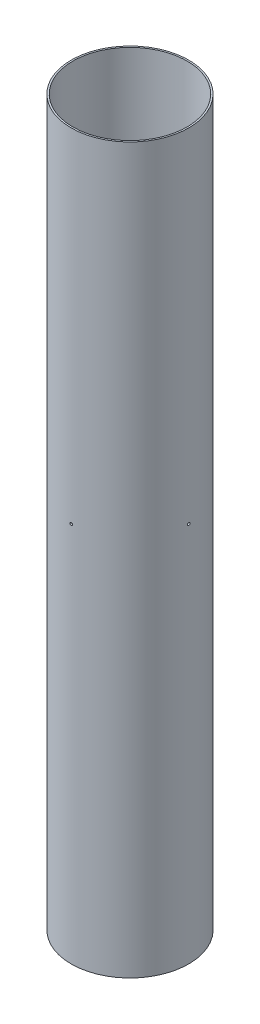
SolidWorks part; units mm, degrees
material "A-Glass Fiber"
ref_plane "Front Plane" through (0, 0, 0) normal (0, 0, 1) x (1, 0, 0)
ref_plane "Top Plane" through (0, 0, 0) normal (0, 1, 0) x (1, 0, 0)
ref_plane "Right Plane" through (0, 0, 0) normal (1, 0, 0) x (0, 0, -1)
sketch "Sketch1" plane through (0, 0, 0) normal (0, 1, 0) x (1, 0, 0)
  circle A0 centre (0, 0) radius 76.1746
  circle A1 centre (0, 0) radius 78.359
  dimension "D1" = 156.718
  dimension "D2" = 152.3492
extrude "Boss-Extrude1" add sketch "Sketch1" along normal blind 965.2
ref_axis "Axis1" through (0, 965.2, 0) along (0, -1, 0)
sketch "Sketch3" plane through (0, 0, 0) normal (0, 0, 1) x (1, 0, 0)
  line L0 (0, 508) -> (0, 965.2) construction
  line L1 (78.359, 965.2) -> (-78.359, 965.2) construction
  circle A0 centre (0, 508) radius 1.75
  dimension "D2" = 3.5
  dimension "D1" = 457.2
extrude "Cut-Extrude1" cut sketch "Sketch3" against normal through all
pattern_circular "CirPattern1" count 4 over 360 about axis through (0, 965.2, 0) along (0, -1, 0) of "Cut-Extrude1"
equation "\"Fwd_Tube_Length\" = 38in"
equation "\"D1@Boss-Extrude1\" = \"Fwd_Tube_Length\""
equation "\"BKHD_Screw_Diam\"= 3.5mm"
equation "\"Fwd_BKHD_From_Top\" = 18in"
equation "\"D2@Sketch3\"=\"BKHD_Screw_Diam\""
equation "\"D1@Sketch3\"=\"Fwd_BKHD_From_Top\""
equation "\"Bodytube_OD\" = 6.17in"
equation "\"Bodytube_ID\" = 5.998in"
equation "\"D2@Sketch1\"=\"Bodytube_ID\""
equation "\"D1@Sketch1\"=\"Bodytube_OD\""
